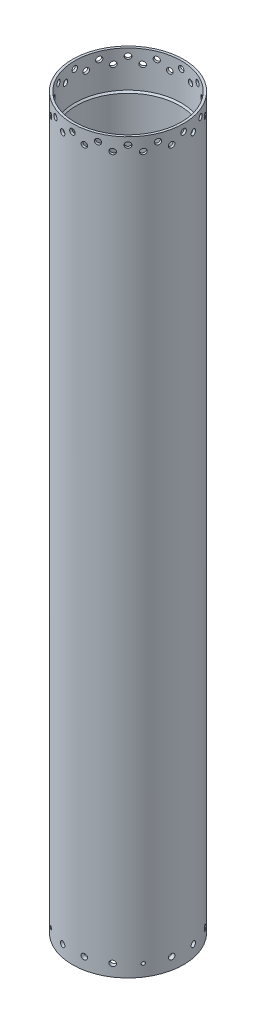
SolidWorks part; units mm, degrees
ref_plane "Płaszczyzna przednia" through (0, 0, 0) normal (0, 0, 1) x (1, 0, 0)
ref_plane "Płaszczyzna górna" through (0, 0, 0) normal (0, 1, 0) x (1, 0, 0)
ref_plane "Płaszczyzna prawa" through (0, 0, 0) normal (1, 0, 0) x (0, 0, -1)
sketch "Szkic1" plane through (0, 0, 0) normal (0, 0, 1) x (1, 0, 0)
  line L0 (0, 552.4394) -> (0, -579.7933) construction
  line L1 (70, -458.5) -> (70, 458.5)
  line L2 (70, 458.5) -> (67, 458.5)
  line L3 (67, 458.5) -> (67, 410.5)
  line L4 (67, 410.5) -> (65, 410.5)
  line L5 (65, 410.5) -> (65, -458.5)
  line L6 (65, -458.5) -> (70, -458.5)
  point P10 (70, 0)
  dimension "D1" = 917
  dimension "D2" = 5
  dimension "D3" = 48
  dimension "D4" = 3
  dimension "D5" = 65
revolve "Obrót1" add sketch "Szkic1" angle 360 about L0
chamfer "Sfazowanie1" distance 2 angle 45 1 edges at (0, 410.5, 67)
ref_plane "Płaszczyzna1" through (0, 0, 70) normal (0, 0, 1) x (1, 0, 0)
sketch "Szkic4" plane through (0, 0, 70) normal (0, 0, 1) x (1, 0, 0)
  line L0 (0, 458.5) -> (0, -458.5) construction
  line L1 (70, 458.5) -> (-70, 458.5) construction
  line L2 (-70, -458.5) -> (70, -458.5) construction
  circle A0 centre (0, 449.5) radius 3.5
  dimension "9" = 9
ref_plane "Płaszczyzna2" through (-13.6563, 0, 68.655) normal (-0.1951, 0, 0.9808) x (0, 1, 0)
sketch "Szkic6" plane through (-13.6563, 0, 68.655) normal (-0.1951, 0, 0.9808) x (0, 1, 0)
  line L0 (458.5, 0) -> (-458.5, 0) construction
  line L1 (458.5, -70) -> (458.5, 70) construction
  line L2 (-458.5, 70) -> (-458.5, -70) construction
  circle A0 centre (441.5, 0) radius 3.5
  dimension "D1" = 17
extrude "Wytnij-wyciągnięcie2" cut sketch "Szkic6" against normal blind 10
pattern_circular "Szyk kołowy2" count 16 over 360 about axis through (0, 552.4394, 0) along (0, 1, 0) of "Wytnij-wyciągnięcie2" reverse direction yes
extrude "Wytnij-wyciągnięcie4" cut sketch "Szkic4" against normal blind 10
pattern_circular "Szyk kołowy3" count 16 over 360 about axis through (0, 552.4394, 0) along (0, 1, 0) of "Wytnij-wyciągnięcie4" reverse direction yes
sketch "Szkic7" plane through (-13.6563, 0, 68.655) normal (-0.1951, 0, 0.9808) x (0, 1, 0)
  line L0 (458.5, 0) -> (-458.5, 0) construction
  line L1 (-458.5, 70) -> (-458.5, -70) construction
  line L2 (458.5, -70) -> (458.5, 70) construction
  circle A0 centre (-443.5, 0) radius 3.5
  dimension "D1" = 15
extrude "Wytnij-wyciągnięcie5" cut sketch "Szkic7" against normal blind 10
pattern_circular "Szyk kołowy4" count 3 over 45 about axis through (0, 552.4394, 0) along (0, 1, 0) of "Wytnij-wyciągnięcie5"
pattern_circular "Szyk kołowy5" count 4 over 360 about axis through (0, 552.4394, 0) along (0, 1, 0) of "Szyk kołowy4"
ref_plane "Płaszczyzna3" through (-58.2029, 0, -38.8899) normal (-0.8315, 0, -0.5556) x (0, 1, 0)
sketch "Szkic11" plane through (-58.2029, 0, -38.8899) normal (-0.8315, 0, -0.5556) x (0, 1, 0)
  line L0 (458.5, 0) -> (-458.5, 0) construction
  line L1 (-458.5, 70) -> (-458.5, -70) construction
  line L2 (458.5, -70) -> (458.5, 70) construction
  circle A0 centre (-443.5, 0) radius 2.05
  dimension "D1" = 15
  dimension "D2" = 4.1
extrude "Wytnij-wyciągnięcie6" cut sketch "Szkic11" against normal blind 10
pattern_circular "Szyk kołowy6" count 4 over 360 about axis through (0, 552.4394, 0) along (0, 1, 0) of "Wytnij-wyciągnięcie6"
